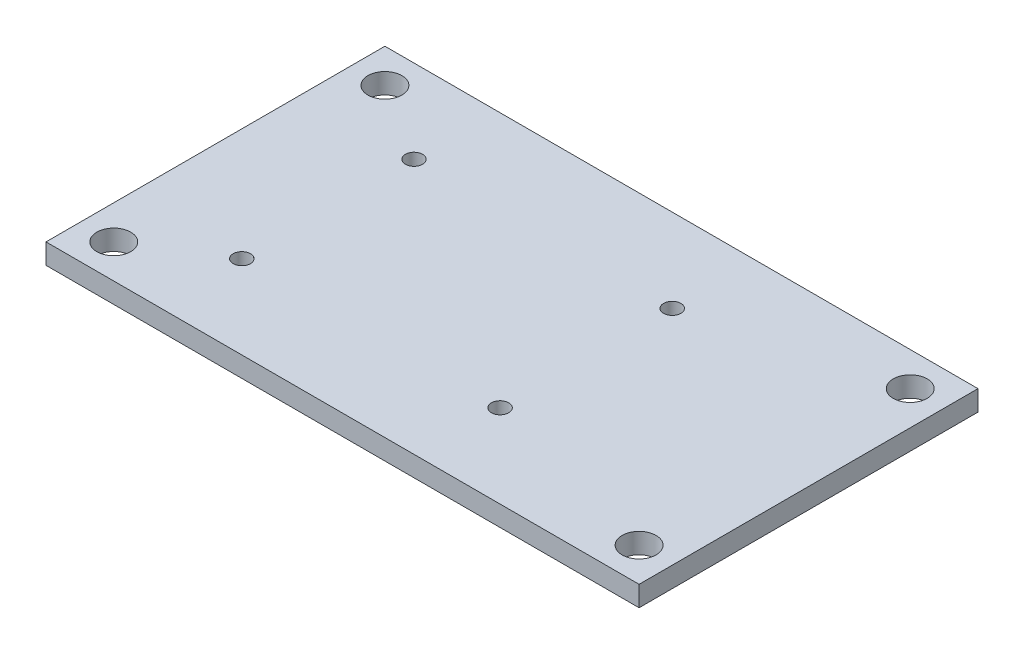
SolidWorks part; units mm, degrees
ref_plane "Front Plane" through (0, 0, 0) normal (0, 0, 1) x (1, 0, 0)
ref_plane "Top Plane" through (0, 0, 0) normal (0, 1, 0) x (1, 0, 0)
ref_plane "Right Plane" through (0, 0, 0) normal (1, 0, 0) x (0, 0, -1)
sketch "Sketch1" plane through (0, 0, 0) normal (0, 1, 0) x (1, 0, 0)
  line L0 (-55, 0) -> (55, 0) construction
  line L1 (-87.5, 50) -> (87.5, 50)
  line L2 (-87.5, 50) -> (-87.5, -50)
  line L3 (-87.5, -50) -> (87.5, -50)
  line L4 (87.5, 50) -> (87.5, -50)
  line L5 (-87.5, 50) -> (87.5, -50) construction
  line L6 (-87.5, -50) -> (87.5, 50) construction
  line L7 (0, -55) -> (0, 55) construction
  circle A0 centre (-77.5, -40) radius 3.175
  circle A1 centre (-77.5, 40) radius 3.175
  circle A2 centre (77.5, 40) radius 3.175
  circle A3 centre (77.5, -40) radius 3.175
  circle A4 centre (-63.5, 25.4) radius 3.175 construction
  circle A5 centre (-63.5, -25.4) radius 3.175 construction
  circle A6 centre (63.5, -25.4) radius 3.175 construction
  circle A7 centre (63.5, 25.4) radius 3.175 construction
  point P0 (0, 0)
  dimension "D3" = 6.35
  dimension "D1" = 100
  dimension "D2" = 175
  dimension "D4" = 40
  dimension "D5" = 77.5
  dimension "D6" = 25.4
  dimension "D7" = 63.5
extrude "Boss-Extrude1" add sketch "Sketch1" along normal blind 6
sketch "Sketch2" plane through (0, 6, 0) normal (0, 1, 0) x (1, 0, 0)
  line L0 (-3.3, 0) -> (3.3, 0) construction
  line L1 (0, -3.3) -> (0, 3.3) construction
  line L2 (-87.5, 50) -> (-87.5, -50) construction
  line L3 (-87.5, 0) -> (87.5, 0) construction
  line L4 (87.5, -50) -> (87.5, 50) construction
  circle A0 centre (-77.5, 40) radius 5
  circle A1 centre (-77.5, -40) radius 5
  circle A2 centre (77.5, -40) radius 5
  circle A3 centre (77.5, 40) radius 5
  circle A8 centre (21.88, -25.4) radius 2.555
  circle A9 centre (-54.32, -25.4) radius 2.555
  circle A10 centre (21.88, 25.4) radius 2.555
  circle A11 centre (-54.32, 25.4) radius 2.555
  dimension "D1" = 10
  dimension "D3" = 65.62
  dimension "D5" = 5.11
  dimension "D2" = 5.11
  dimension "D4" = 76.2
  dimension "D6" = 25.4
  dimension "D7" = 50.8
extrude "Cut-Extrude1" cut sketch "Sketch2" against normal through all
